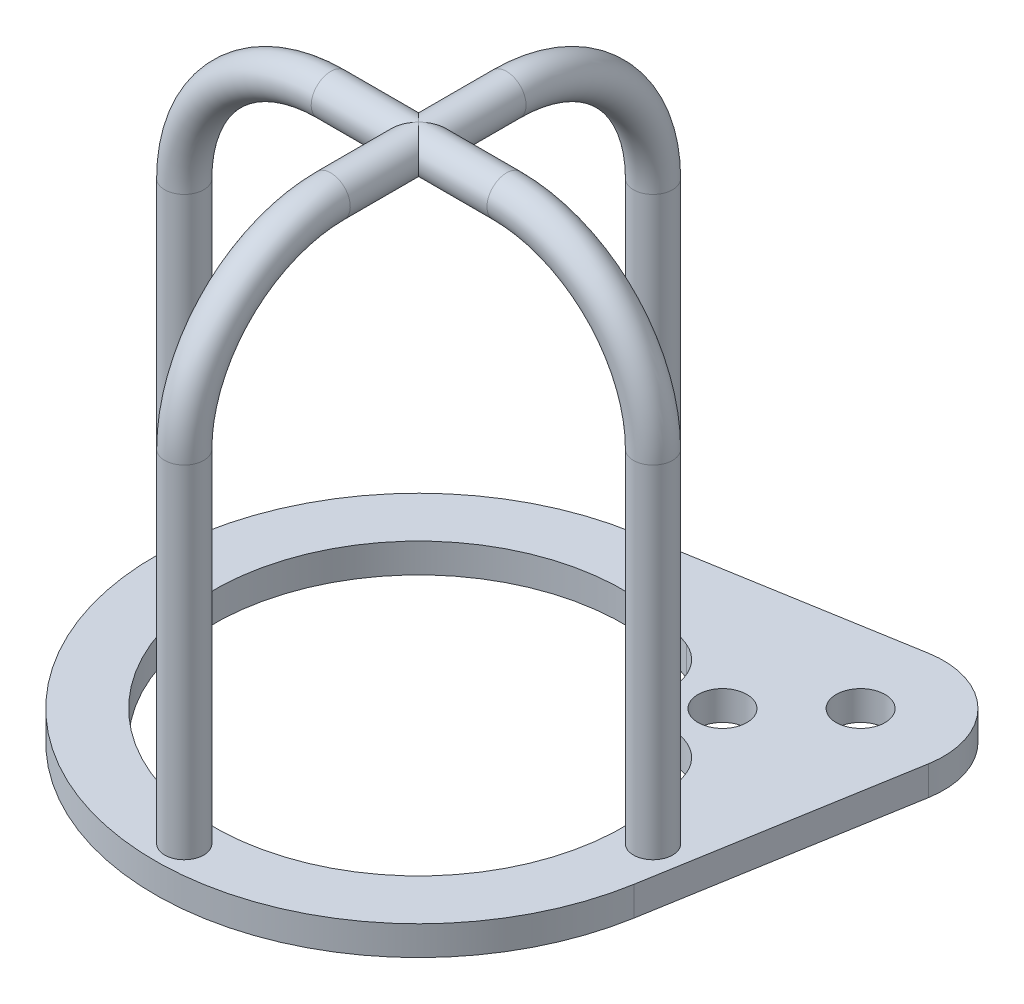
SolidWorks part; units mm, degrees
ref_plane "Plan de face" through (0, 0, 0) normal (0, 0, 1) x (1, 0, 0)
ref_plane "Plan de dessus" through (0, 0, 0) normal (0, 1, 0) x (1, 0, 0)
ref_plane "Plan de droite" through (0, 0, 0) normal (1, 0, 0) x (0, 0, -1)
sketch "Esquisse1" plane through (0, 0, 0) normal (0, 0, 1) x (1, 0, 0)
  line L0 (0, 50) -> (9, 50)
  line L1 (24, 35) -> (24, 0)
  line L2 (0, 0) -> (0, 50) construction
  line L3 (0, 0) -> (24, 0) construction
  arc A0 (24, 35) -> (9, 50) centre (9, 35) ccw
  dimension "D1" = 15
  dimension "D2" = 24
  dimension "D3" = 50
sketch "Esquisse2" plane through (0, 0, 0) normal (0, 1, 0) x (1, 0, 0)
  line L0 (9, 0) -> (24, 0) construction
  line L1 (0, 0) -> (24, 0) construction
  circle A0 centre (24, 0) radius 2
  dimension "D1" = 4
  dimension "D2" = 24
sweep "Balayage1" add profiles "Esquisse2" path "Esquisse1"
sketch "Esquisse3" plane through (0, 0, 0) normal (0, 0, 1) x (1, 0, 0)
  line L0 (0, 0) -> (0, 50) construction
  line L1 (0, 52) -> (0, 48) construction
pattern_circular "Répétition circulaire1" count 4 over 360 about axis through (0, 0, 0) along (0, 1, 0) of "Balayage1" reverse direction yes
sketch "Esquisse4" plane through (0, 0, 0) normal (0, -1, 0) x (1, 0, 0)
  line L0 (0, 0) -> (33.2746, -33.2746) construction
  line L1 (0, 0) -> (0, -27) construction
  line L2 (26.6155, 4.5405) -> (31.0064, -21.198)
  line L3 (21.198, -31.0064) -> (-4.5405, -26.6155)
  circle A0 centre (0, 0) radius 21 construction
  circle A1 centre (0, 0) radius 27 construction
  circle A2 centre (15.5563, -15.5563) radius 2.5
  circle A3 centre (22.6274, -22.6274) radius 2.5
  arc A4 (31.0064, -21.198) -> (21.198, -31.0064) centre (22.6274, -22.6274) cw
  arc A5 (11.5246, -17.5551) -> (17.5551, -11.5246) centre (15.5563, -15.5563) cw
  arc A6 (17.5551, -11.5246) -> (11.5246, -17.5551) centre (0, 0) ccw
  arc A7 (26.6155, 4.5405) -> (-4.5405, -26.6155) centre (0, 0) ccw
  dimension "D1" = 42
  dimension "D2" = 6
  dimension "D3" = 45
  dimension "D6" = 5
  dimension "D7" = 6
  dimension "D8" = 2
  dimension "D4" = 22
  dimension "D5" = 10
extrude "Boss.-Extru.1" add sketch "Esquisse4" along normal blind 3
fillet "Congé1" radius 5 2 edges at (17.5551, -1.5, -11.5246) (11.5246, -1.5, -17.5551)
